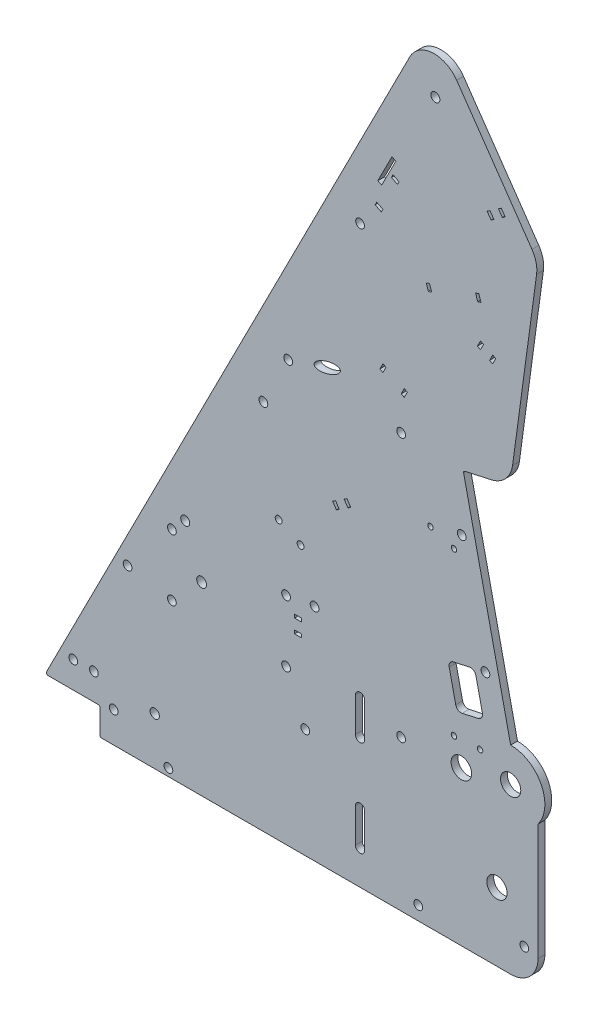
SolidWorks part; units mm, degrees
other "Markup1"
sketch "Sketch5"
ref_plane "Front Plane" through (0, 0, 0) normal (0, 0, 1) x (1, 0, 0)
ref_plane "Top Plane" through (0, 0, 0) normal (0, 1, 0) x (1, 0, 0)
ref_plane "Right Plane" through (0, 0, 0) normal (1, 0, 0) x (0, 0, -1)
sketch "Sketch1" plane through (0, 0, 0) normal (0, 0, 1) x (1, 0, 0)
  line L1 (228.6, -12.7) -> (228.6, 53.975)
  line L2 (178.7547, 351.4131) -> (0, 0)
  line L3 (228.6, 279.4) -> (178.7547, 351.4131)
  line L5 (0, 0) -> (25.4, 0)
  line L6 (25.4, 0) -> (25.4, -12.7)
  line L7 (25.4, -12.7) -> (228.6, -12.7)
  line L9 (215.9, 79.375) -> (193.9097, 178.5667)
  line L10 (193.9097, 178.5667) -> (215.6079, 183.377)
  line L11 (215.6079, 183.377) -> (228.6, 279.4)
  arc A0 (228.6, 53.975) -> (215.9, 79.375) centre (215.9, 63.5) ccw
  dimension "D7" = 12.7
  dimension "D8" = 76.2
  dimension "D10" = 31.75
  dimension "D2" = 292.1
  dimension "D3" = 25.4
  dimension "D4" = 215.9
  dimension "D5" = 394.2644
  dimension "D6" = 203.2
  dimension "D9" = 63.039
  dimension "D11" = 101.6
  dimension "D12" = 12.5
  dimension "D13" = 22.225
extrude "Boss-Extrude1" add sketch "Sketch1" along normal blind 3.175
sketch "Sketch2" plane through (0, 0, 3.175) normal (0, 0, 1) x (1, 0, 0)
  line L0 (178.7547, 351.4131) -> (0, 0) construction
  line L1 (25.4, -12.7) -> (228.6, -12.7) construction
  line L2 (215.9, 79.375) -> (193.9097, 178.5667) construction
  line L3 (193.9097, 178.5667) -> (215.6079, 183.377) construction
  line L4 (215.9, 79.375) -> (193.9097, 178.5667) construction
  line L5 (64.9432, 94.0578) -> (72.5445, 73.1732) construction
  line L6 (64.9432, 94.0578) -> (103.3734, 94.0578) construction
  line L10 (228.6, -12.7) -> (228.6, 53.975) construction
  circle A0 centre (64.9432, 94.0578) radius 2.0955
  circle A1 centre (180.975, 322.1643) radius 2.0955
  circle A2 centre (72.5445, 73.1732) radius 2.286
  circle A3 centre (193.2078, 152.3944) radius 2.032
  circle A4 centre (215.9, 63.5) radius 4.699
  circle A7 centre (173.0375, -6.35) radius 2.032
  circle A8 centre (204.203, 102.7985) radius 2.032
  circle A26 centre (209.55, 19.05) radius 4.699
  arc A30 (228.6, 53.975) -> (215.9, 79.375) centre (215.9, 63.5) ccw construction
  circle A31 centre (165.1, 179.3875) radius 2.032
  circle A35 centre (111.724, 87.4607) radius 2.032
  circle A36 centre (111.724, 58.8857) radius 2.032
  circle A37 centre (58.765, 58.8857) radius 2.032
  circle A38 centre (58.765, 87.4607) radius 2.032
  circle A39 centre (111.724, 58.8857) radius 1.905 construction
  circle A42 centre (111.724, 87.4607) radius 1.905 construction
  circle A43 centre (58.765, 58.8857) radius 1.905 construction
  circle A44 centre (58.765, 87.4607) radius 1.905 construction
  point P50 (78.0779, 111.9863)
  point P51 (78.3895, 76.3619)
  dimension "D3" = 4.191
  dimension "D5" = 4.191
  dimension "D9" = 4.572
  dimension "D20" = 9.398
  dimension "D23" = 9.398
  dimension "D18" = 4.064
  dimension "D26" = 4.064
  dimension "D14" = 4.064
  dimension "D10" = 4.064
  dimension "D2" = 15.24
  dimension "D6" = 15.24
  dimension "D7" = 22.225
  dimension "D21" = 44.45
  dimension "D22" = 6.35
  dimension "D19" = 160.3375
  dimension "D24" = 44.45
  dimension "D25" = 6.35
  dimension "D27" = 25.4
  dimension "D28" = 50.8
  dimension "D29" = 6.35
  dimension "D17" = 6.35
  dimension "D33" = 55.5625
  dimension "D15" = 114.3
  dimension "D4" = 180.975
  dimension "D8" = 70
extrude "Cut-Extrude1" cut sketch "Sketch2" against normal through all
sketch "Sketch7" plane through (0, 0, 3.175) normal (0, 0, 1) x (1, 0, 0)
  line L0 (146.05, 3.175) -> (146.05, 19.05) construction
  line L1 (143.891, 3.175) -> (143.891, 19.05)
  line L2 (148.209, 3.175) -> (148.209, 19.05)
  line L3 (146.05, 47.625) -> (146.05, 63.5) construction
  line L4 (143.891, 47.625) -> (143.891, 63.5)
  line L5 (148.209, 47.625) -> (148.209, 63.5)
  line L6 (25.4, -12.7) -> (228.6, -12.7) construction
  line L12 (228.6, -12.7) -> (228.6, 53.975) construction
  line L13 (25.4, -12.7) -> (228.6, -12.7) construction
  arc A0 (143.891, 3.175) -> (148.209, 3.175) centre (146.05, 3.175) ccw
  arc A1 (148.209, 19.05) -> (143.891, 19.05) centre (146.05, 19.05) ccw
  arc A2 (143.891, 47.625) -> (148.209, 47.625) centre (146.05, 47.625) ccw
  arc A3 (148.209, 63.5) -> (143.891, 63.5) centre (146.05, 63.5) ccw
  circle A8 centre (50.8, 9.525) radius 2.159
  point P2 (146.05, 11.1125)
  point P9 (146.05, 55.5625)
  dimension "D1" = 4.318
  dimension "D5" = 4.318
  dimension "D2" = 15.875
  dimension "D3" = 15.875
  dimension "D4" = 44.45
  dimension "D6" = 95.25
  dimension "D7" = 82.55
  dimension "D8" = 15.875
  dimension "D9" = 22.225
extrude "Cut-Extrude2" cut sketch "Sketch7" against normal through all
sketch "Sketch10" plane through (0, 0, 3.175) normal (0, 0, 1) x (1, 0, 0)
  circle A0 centre (120.65, 38.1) radius 2.032
  circle A1 centre (165.1, 57.15) radius 2.032
  circle A2 centre (13.0465, 12.3347) radius 2.032
  circle A3 centre (22.5715, 12.3347) radius 2.032
  circle A4 centre (38.2114, 62.6398) radius 2.032
  circle A5 centre (13.0465, 12.3347) radius 2.032 construction
  circle A6 centre (22.5715, 12.3347) radius 2.032 construction
  dimension "D1" = 4.064
  dimension "D3" = 38.1
  dimension "D2" = 120.65
  dimension "D4" = 63.5
  dimension "D5" = 69.85
extrude "Cut-Extrude3" cut sketch "Sketch10" against normal up to next
fillet "Fillet1" radius 12.7 4 edges at (228.6, -12.7, 1.5875) (178.7547, 351.4131, 1.5875) (215.6079, 183.377, 1.5875) (228.6, 279.4, 1.5875)
fillet "Fillet2" radius 0.7937 4 edges at (25.4, -12.7, 1.5875) (25.4, 0, 1.5875) (193.9097, 178.5667, 1.5875) (0, 0, 1.5875)
sketch "Sketch12" plane through (0, 0, 3.175) normal (0, 0, 1) x (1, 0, 0)
  circle A0 centre (31.75, 1.5875) radius 2.032
  circle A1 centre (173.0375, -6.35) radius 2.032
  circle A2 centre (222.25, 1.5875) radius 2.032
  circle A3 centre (57.15, -9.2075) radius 2.032
  circle A4 centre (57.15, -9.2075) radius 2.286 construction
  dimension "D1" = 4.064
  dimension "D2" = 4.064
extrude "Cut-Extrude5" cut sketch "Sketch12" against normal through all
sketch "Sketch13" plane through (0, 0, 3.175) normal (0, 0, 1) x (1, 0, 0)
  line L1 (228.6, 0) -> (228.6, 53.975) construction
  line L2 (1.2943, 0) -> (24.6062, 0) construction
  line L3 (26.1937, -12.7) -> (215.9, -12.7) construction
  line L8 (178.2697, 245.9923) -> (176.7582, 245.5069)
  line L9 (179.2404, 242.9693) -> (178.2697, 245.9923)
  line L10 (177.7289, 242.4839) -> (179.2404, 242.9693)
  line L11 (176.7582, 245.5069) -> (177.7289, 242.4839)
  line L12 (178.2697, 245.9923) -> (176.7582, 245.5069)
  line L13 (179.2404, 242.9693) -> (178.2697, 245.9923)
  line L14 (177.7289, 242.4839) -> (179.2404, 242.9693)
  line L15 (176.7582, 245.5069) -> (177.7289, 242.4839)
  line L16 (160.8477, 288.1984) -> (154.2836, 275.294)
  line L17 (200.6096, 249.8308) -> (202.1211, 250.3161)
  line L18 (199.639, 252.8538) -> (200.6096, 249.8308)
  line L19 (201.1505, 253.3391) -> (199.639, 252.8538)
  line L20 (202.1211, 250.3161) -> (201.1505, 253.3391)
  line L21 (200.6096, 249.8308) -> (202.1211, 250.3161)
  line L22 (199.639, 252.8538) -> (200.6096, 249.8308)
  line L23 (201.1505, 253.3391) -> (199.639, 252.8538)
  line L24 (202.1211, 250.3161) -> (201.1505, 253.3391)
  line L25 (160.8477, 288.1984) -> (162.6303, 287.2917)
  line L26 (160.5905, 279.7801) -> (163.4204, 278.3406)
  line L27 (161.3102, 281.1951) -> (160.5905, 279.7801)
  line L28 (164.1402, 279.7556) -> (161.3102, 281.1951)
  line L29 (163.4204, 278.3406) -> (164.1402, 279.7556)
  line L30 (160.5905, 279.7801) -> (163.4204, 278.3406)
  line L31 (161.3102, 281.1951) -> (160.5905, 279.7801)
  line L32 (164.1402, 279.7556) -> (161.3102, 281.1951)
  line L33 (163.4204, 278.3406) -> (164.1402, 279.7556)
  line L34 (154.2836, 275.294) -> (156.0662, 274.3872)
  line L35 (162.6303, 287.2917) -> (156.0662, 274.3872)
  line L36 (153.7897, 266.4104) -> (153.0699, 264.9954)
  line L37 (156.6196, 264.9709) -> (153.7897, 266.4104)
  line L38 (155.8998, 263.5559) -> (156.6196, 264.9709)
  line L39 (153.0699, 264.9954) -> (155.8998, 263.5559)
  line L40 (153.7897, 266.4104) -> (153.0699, 264.9954)
  line L41 (156.6196, 264.9709) -> (153.7897, 266.4104)
  line L42 (155.8998, 263.5559) -> (156.6196, 264.9709)
  line L43 (153.0699, 264.9954) -> (155.8998, 263.5559)
  line L110 (153.9925, 274.7218) -> (157.3929, 281.4066) construction
  line L111 (155.7751, 273.815) -> (159.1755, 280.4999) construction
  line L122 (203.3303, 234.0299) -> (201.9154, 234.7497)
  line L123 (201.8908, 231.2) -> (203.3303, 234.0299)
  line L124 (200.4759, 231.9198) -> (201.8908, 231.2)
  line L125 (201.9154, 234.7497) -> (200.4759, 231.9198)
  line L126 (203.3303, 234.0299) -> (201.9154, 234.7497)
  line L127 (201.8908, 231.2) -> (203.3303, 234.0299)
  line L128 (200.4759, 231.9198) -> (201.8908, 231.2)
  line L129 (201.9154, 234.7497) -> (200.4759, 231.9198)
  line L130 (206.1357, 229.0407) -> (207.5507, 228.321)
  line L131 (207.5752, 231.8707) -> (206.1357, 229.0407)
  line L132 (208.9902, 231.1509) -> (207.5752, 231.8707)
  line L133 (207.5507, 228.321) -> (208.9902, 231.1509)
  line L134 (206.1357, 229.0407) -> (207.5507, 228.321)
  line L135 (207.5752, 231.8707) -> (206.1357, 229.0407)
  line L136 (208.9902, 231.1509) -> (207.5752, 231.8707)
  line L137 (207.5507, 228.321) -> (208.9902, 231.1509)
  line L138 (211.5405, 292.889) -> (210.2352, 291.9855)
  line L139 (213.3475, 290.2784) -> (211.5405, 292.889)
  line L140 (212.0422, 289.3749) -> (213.3475, 290.2784)
  line L141 (210.2352, 291.9855) -> (212.0422, 289.3749)
  line L142 (211.5405, 292.889) -> (210.2352, 291.9855)
  line L143 (213.3475, 290.2784) -> (211.5405, 292.889)
  line L144 (212.0422, 289.3749) -> (213.3475, 290.2784)
  line L145 (210.2352, 291.9855) -> (212.0422, 289.3749)
  line L146 (206.3193, 289.275) -> (205.014, 288.3715)
  line L147 (208.1263, 286.6644) -> (206.3193, 289.275)
  line L148 (206.821, 285.7609) -> (208.1263, 286.6644)
  line L149 (205.014, 288.3715) -> (206.821, 285.7609)
  line L150 (206.3193, 289.275) -> (205.014, 288.3715)
  line L151 (208.1263, 286.6644) -> (206.3193, 289.275)
  line L152 (206.821, 285.7609) -> (208.1263, 286.6644)
  line L153 (205.014, 288.3715) -> (206.821, 285.7609)
  line L184 (133.3504, 136.102) -> (135.0815, 133.4404)
  line L185 (133.3504, 136.102) -> (134.6812, 136.9675)
  line L186 (135.0815, 133.4404) -> (136.4123, 134.3059)
  line L187 (155.2281, 200.1197) -> (156.643, 199.3999)
  line L188 (156.6676, 202.9496) -> (155.2281, 200.1197)
  line L189 (158.0826, 202.2298) -> (156.6676, 202.9496)
  line L190 (156.643, 199.3999) -> (158.0826, 202.2298)
  line L191 (155.2281, 200.1197) -> (156.643, 199.3999)
  line L192 (156.6676, 202.9496) -> (155.2281, 200.1197)
  line L193 (158.0826, 202.2298) -> (156.6676, 202.9496)
  line L194 (156.643, 199.3999) -> (158.0826, 202.2298)
  line L195 (134.6812, 136.9675) -> (136.4123, 134.3059)
  line L196 (165.1328, 195.0814) -> (166.5478, 194.3617)
  line L197 (166.5723, 197.9113) -> (165.1328, 195.0814)
  line L198 (167.9873, 197.1916) -> (166.5723, 197.9113)
  line L199 (166.5478, 194.3617) -> (167.9873, 197.1916)
  line L200 (165.1328, 195.0814) -> (166.5478, 194.3617)
  line L201 (166.5723, 197.9113) -> (165.1328, 195.0814)
  line L202 (167.9873, 197.1916) -> (166.5723, 197.9113)
  line L203 (166.5478, 194.3617) -> (167.9873, 197.1916)
  line L204 (140.4047, 136.9025) -> (138.6737, 139.5641)
  line L205 (140.4047, 136.9025) -> (141.7355, 137.768)
  line L206 (138.6737, 139.5641) -> (140.0045, 140.4296)
  line L207 (141.7355, 137.768) -> (140.0045, 140.4296)
  line L209 (169.1053, 332.4434) -> (0.5868, 1.1536) construction
  line L210 (88.0466, 102.1523) -> (85.2167, 103.5918) construction
  line L288 (115.661, 81.8727) -> (118.836, 81.8727)
  line L289 (115.661, 81.8727) -> (115.661, 80.2852)
  line L290 (118.836, 81.8727) -> (118.836, 80.2852)
  line L291 (115.661, 80.2852) -> (118.836, 80.2852)
  line L292 (115.661, 75.5227) -> (118.836, 75.5227)
  line L293 (115.661, 75.5227) -> (115.661, 73.9352)
  line L294 (118.836, 75.5227) -> (118.836, 73.9352)
  line L295 (115.661, 73.9352) -> (118.836, 73.9352)
  line L297 (115.661, 86.2542) -> (115.661, 60.0922) construction
  line L298 (59.9715, 91.3977) -> (110.5175, 91.3977) construction
  circle A0 centre (112.7125, 182.5625) radius 2.032
  circle A1 centre (146.05, 254) radius 2.032
  circle A2 centre (101.1964, 159.9231) radius 2.032 construction
  circle A3 centre (101.1964, 159.9231) radius 2.032
  circle A4 centre (-8.8402, -85.5324) radius 1.6 construction
  circle A5 centre (-3.6715, -75.3714) radius 1.6 construction
  circle A7 centre (-8.8402, -85.5324) radius 1.6
  circle A8 centre (-3.6715, -75.3714) radius 1.6
  circle A9 centre (108.294, 116.1502) radius 1.6 construction
  circle A10 centre (118.455, 110.9816) radius 1.6 construction
  circle A11 centre (108.294, 116.1502) radius 1.6
  circle A12 centre (118.455, 110.9816) radius 1.6
  ellipse E0 centre (130.8261, 188.4615) end of major axis (136.864, 190.4279) minor radius 2.3812 construction
  ellipse E1 centre (130.8261, 188.4615) end of major axis (136.864, 190.4279) minor radius 2.3812
  dimension "D2" = 4.064
  dimension "D5" = 4.064
  dimension "D1" = 195.2625
  dimension "D3" = 82.55
  dimension "D4" = 254
  dimension "D6" = 115.8875
  dimension "D11" = 7.62
  dimension "D12" = 6.858
  dimension "D13" = 1.5875
  dimension "D14" = 3.175
  dimension "D15" = 4.7625
  dimension "D16" = 60
  dimension "D17" = 57.15
  dimension "D24" = 50.8
  dimension "D29" = 3.175
  dimension "D30" = 1.5875
  dimension "D31" = 4.7625
  dimension "D32" = 0
  dimension "D33" = 9.525
  dimension "D7" = 0
  dimension "D8" = 0
  dimension "D9" = 0
  dimension "D10" = 0
  dimension "D18" = 0
  dimension "D19" = 0
  dimension "D20" = 0
  dimension "D21" = 0
  dimension "D22" = 0
  dimension "D23" = 0
extrude "Cut-Extrude6" cut sketch "Sketch13" against normal through all
sketch "Sketch14" plane through (0, 0, 3.175) normal (0, 0, 1) x (1, 0, 0)
  line L5 (186.8444, 98.9502) -> (199.2434, 101.699)
  line L6 (186.8444, 98.9502) -> (190.9676, 80.3518)
  line L7 (190.9676, 80.3518) -> (203.3665, 83.1006)
  line L8 (199.2434, 101.699) -> (203.3665, 83.1006)
  line L14 (202.8168, 85.5804) -> (199.7931, 99.2192) construction
  line L15 (193.4474, 80.9015) -> (200.8868, 82.5508) construction
  line L16 (187.3942, 96.4704) -> (190.4178, 82.8316) construction
  line L17 (196.7636, 101.1493) -> (189.3242, 99.5) construction
  circle A0 centre (189.6022, 69.9806) radius 1.27
  circle A1 centre (201.7089, 70.5092) radius 1.27
  circle A2 centre (189.6022, 69.9806) radius 1.27 construction
  circle A3 centre (201.7089, 70.5092) radius 1.27 construction
  circle A4 centre (165.1, 57.15) radius 2.032
  circle A5 centre (124.9491, 89.5852) radius 2.032
  circle A6 centre (178.7216, 148.5324) radius 1.27
  circle A8 centre (178.7216, 148.5324) radius 1.27 construction
  circle A9 centre (189.6226, 145.0954) radius 1.27
  circle A10 centre (189.6226, 145.0954) radius 1.27 construction
  point P8 (152.4, 88.9)
  dimension "D1" = 4.064
extrude "Cut-Extrude7" cut sketch "Sketch14" against normal through all both and the other way through all
fillet "Fillet3" radius 2.54 4 edges at (199.2434, 101.699, 1.5875) (186.8444, 98.9502, 1.5875) (190.9676, 80.3518, 1.5875) (203.3665, 83.1006, 1.5875)
sketch "Sketch15" plane through (0, 0, 3.175) normal (0, 0, 1) x (1, 0, 0)
  circle A0 centre (193.04, 58.801) radius 4.7625 construction
  circle A1 centre (193.04, 58.801) radius 4.7625
extrude "Cut-Extrude8" cut sketch "Sketch15" against normal through all
equation "\"D6@Sketch2\"=\"D2@Sketch2\""
